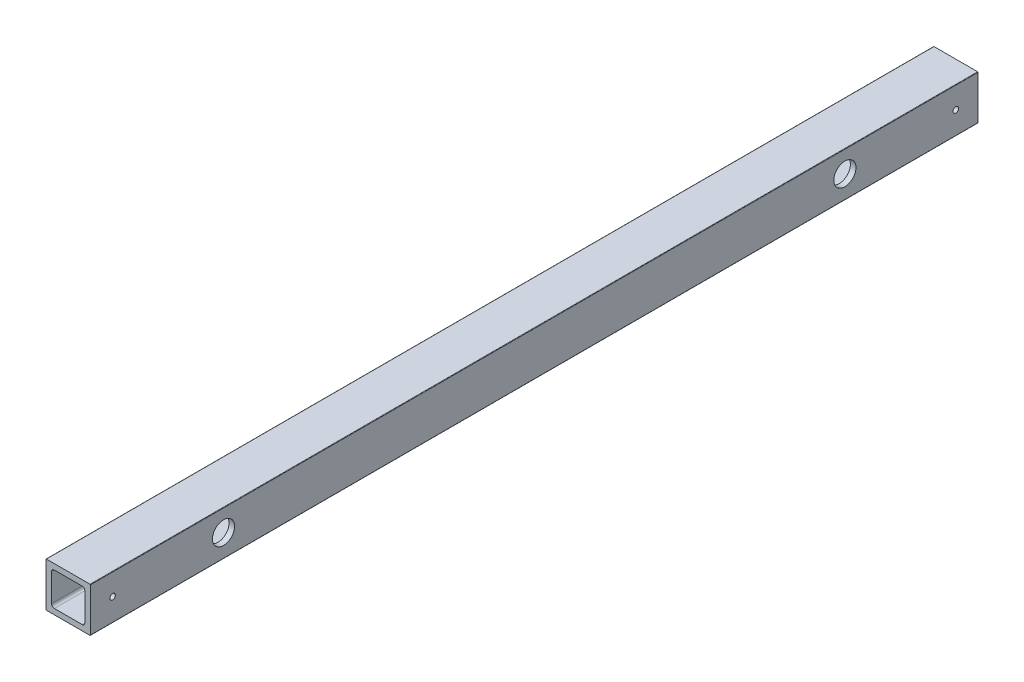
SolidWorks part; units mm, degrees
ref_plane "Front Plane" through (0, 0, 0) normal (0, 0, 1) x (1, 0, 0)
ref_plane "Top Plane" through (0, 0, 0) normal (0, 1, 0) x (1, 0, 0)
ref_plane "Right Plane" through (0, 0, 0) normal (1, 0, 0) x (0, 0, -1)
ref_plane "Plane1" through (0, 0, 0) normal (0, 0, -1) x (-1, 0, 0)
sketch "Sketch1" plane through (0, 0, 0) normal (0, 0, -1) x (-1, 0, 0)
  line L0 (-3.175, 20.6375) -> (-3.175, 4.7625)
  line L1 (-4.7625, 3.175) -> (-20.6375, 3.175)
  line L2 (-22.225, 4.7625) -> (-22.225, 20.6375)
  line L3 (-20.6375, 22.225) -> (-4.7625, 22.225)
  line L4 (0, 0.254) -> (0, 25.146)
  line L5 (-0.254, 25.4) -> (-25.146, 25.4)
  line L6 (-25.4, 25.146) -> (-25.4, 0.254)
  line L7 (-25.146, 0) -> (-0.254, 0)
  arc A0 (-3.175, 4.7625) -> (-4.7625, 3.175) centre (-4.7625, 4.7625) cw
  arc A1 (-20.6375, 3.175) -> (-22.225, 4.7625) centre (-20.6375, 4.7625) cw
  arc A2 (-22.225, 20.6375) -> (-20.6375, 22.225) centre (-20.6375, 20.6375) cw
  arc A3 (-4.7625, 22.225) -> (-3.175, 20.6375) centre (-4.7625, 20.6375) cw
  arc A4 (-0.254, 0) -> (0, 0.254) centre (-0.254, 0.254) ccw
  arc A5 (0, 25.146) -> (-0.254, 25.4) centre (-0.254, 25.146) ccw
  arc A6 (-25.146, 25.4) -> (-25.4, 25.146) centre (-25.146, 25.146) ccw
  arc A7 (-25.4, 0.254) -> (-25.146, 0) centre (-25.146, 0.254) ccw
  dimension "D1" = 25.4
  dimension "D2" = 25.4
  dimension "D3" = 19.05
  dimension "D4" = 3.175
  dimension "D5" = 19.05
extrude "Boss-Extrude1" add sketch "Sketch1" against normal blind 508
sketch "Sketch2" plane through (0, 0, 0) normal (-1, 0, 0) x (0, 0, 1)
  line L0 (0, 0.254) -> (0, 25.146) construction
  line L1 (508, 0.254) -> (0, 0.254) construction
  line L2 (508, 0.254) -> (508, 25.146) construction
  circle A0 centre (12.6975, 12.954) radius 1.5875
  circle A1 centre (495.3, 12.954) radius 1.5875
  circle A2 centre (76.2, 12.954) radius 6.35
  circle A3 centre (431.8, 12.954) radius 6.35
  point P4 (0, 12.7)
  dimension "D1" = 3.175
  dimension "D2" = 12.7
  dimension "D3" = 12.7
  dimension "D4" = 3.175
  dimension "D5" = 12.7
  dimension "D6" = 12.7
  dimension "D7" = 12.7
  dimension "D8" = 12.7
  dimension "D9" = 76.2
  dimension "D10" = 12.7
  dimension "D11" = 12.7
  dimension "D12" = 76.2
extrude "Cut-Extrude1" cut sketch "Sketch2" against normal through all
